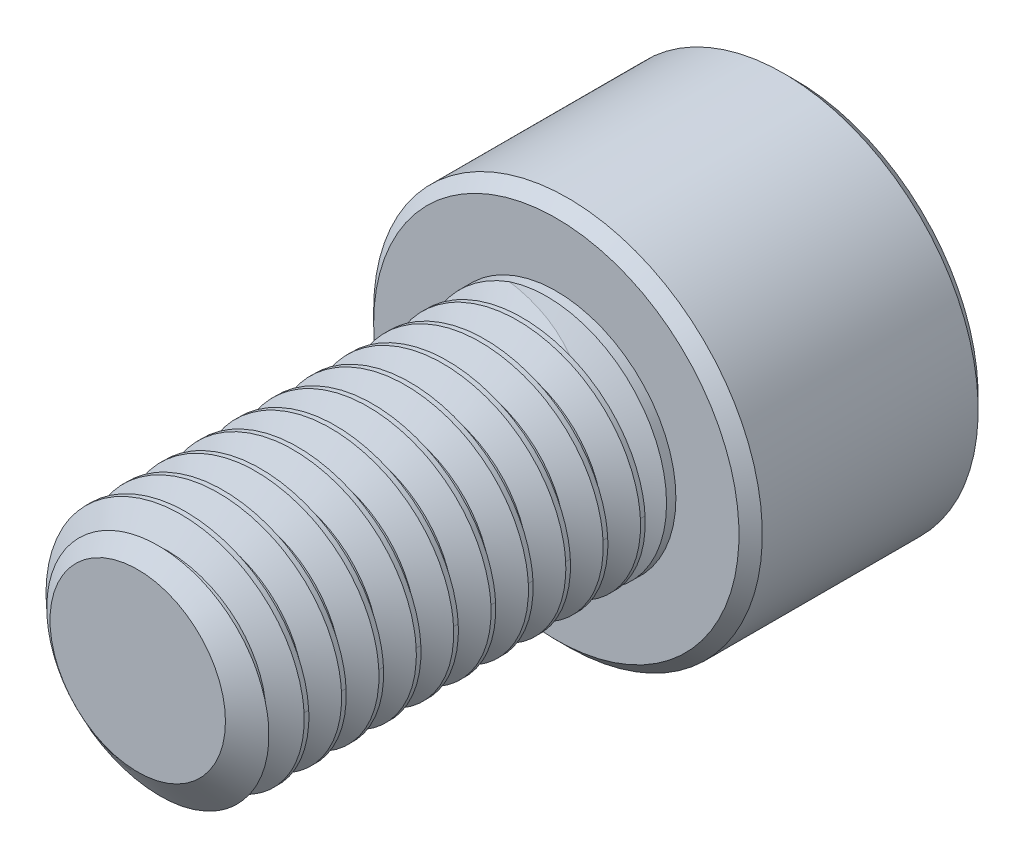
SolidWorks part; units mm, degrees
ref_plane "Front Plane" through (0, 0, 0) normal (0, 0, 1) x (1, 0, 0)
ref_plane "Top Plane" through (0, 0, 0) normal (0, 1, 0) x (1, 0, 0)
ref_plane "Right Plane" through (0, 0, 0) normal (1, 0, 0) x (0, 0, -1)
sketch "Sketch1" plane through (0, 0, 0) normal (0, 0, 1) x (1, 0, 0)
  circle A0 centre (0, 0) radius 4
  dimension "OD" = 8
extrude "Extrude1" add sketch "Sketch1" against normal blind 14
sketch "Sketch2" plane through (0, 0, 0) normal (0, 0, 1) x (1, 0, 0)
  circle A0 centre (0, 0) radius 4 construction
  circle A1 centre (0, 0) radius 4
curve "Helix/Spiral1" pitch 1.25 height 15.25 turns 12.2 parameters "pitch"=1.25
sketch "Sketch3" plane through (0, 0, 0) normal (1, 0, 0) x (0, 0, -1)
  line L0 (-1.0938, 4) -> (-0.625, 3.1881)
  line L1 (-0.625, 3.1881) -> (-0.4688, 3.1881)
  line L2 (-0.4688, 3.1881) -> (0, 4)
  line L3 (-1.0938, 4) -> (0, 4)
  line L4 (-0.5469, 4) -> (-0.5469, 3.1881) construction
  line L5 (-0.8594, 3.5941) -> (-0.2344, 3.5941) construction
  line L6 (0, 4) -> (0, -4) construction
  line L7 (0, -4) -> (14, -4) construction
  point P11 (5.625, -4)
  dimension "D1" = 0.1562
  dimension "D2" = 0.625
  dimension "D3" = 60
  dimension "D4" = 5.625
sweep "Cut-Sweep1" cut profiles "Sketch3" path "Helix/Spiral1"
sketch "Sketch4" plane through (0, 0, 0) normal (1, 0, 0) x (0, 0, -1)
  line L0 (0.7464, 4) -> (0, 2.9341)
  line L1 (0, 2.9341) -> (0, 4)
  line L2 (0.7464, 4) -> (0, 4)
  line L3 (-1.0938, 4) -> (0, 4) construction
  line L4 (0, 0) -> (7.0209, 0) construction
  dimension "D1" = 55
  dimension "D2" = 0.254
revolve "Cut-Revolve1" cut sketch "Sketch4" angle 360 about L4
sketch "Sketch5" plane through (0, 0, 0) normal (1, 0, 0) x (0, 0, -1)
  line L0 (14, -0.9564) -> (14, 3.8508) construction
  line L1 (14, 4) -> (0.1203, 4)
  line L2 (14, 4) -> (14, 0)
  line L3 (14, 0) -> (0.0001, 0)
  line L4 (0.0001, 3.6698) -> (0.0001, 0)
  line L5 (0.1203, 4) -> (0.0001, 3.6698)
  line L6 (0, 0) -> (9.9695, 0) construction
  point P3 (0.0001, 4)
  point P10 (0.0001, 4)
  dimension "D1" = 0.3302
  dimension "Thread min" = 0.0001
  dimension "D3" = 20
revolve "partially thread" [suppressed] add sketch "Sketch5" angle 360 about L6
sketch "Sketch6" plane through (0, 0, -14) normal (0, 0, -1) x (-1, 0, 0)
  circle A0 centre (0, 0) radius 6.5
  dimension "head dia" = 13
extrude "Extrude2" add sketch "Sketch6" along normal blind 8
sketch "Sketch7" plane through (0, 0, -22) normal (0, 0, -1) x (-1, 0, 0)
  line L1 (0, 3.4641) -> (-3, 1.7321)
  line L2 (-3, 1.7321) -> (-3, -1.7321)
  line L3 (-3, -1.7321) -> (0, -3.4641)
  line L4 (0, -3.4641) -> (3, -1.7321)
  line L5 (3, -1.7321) -> (3, 1.7321)
  line L6 (3, 1.7321) -> (0, 3.4641)
  circle A0 centre (0, 0) radius 3 construction
  dimension "hex dia" = 6
extrude "Cut-Extrude1" cut sketch "Sketch7" against normal blind 4.5
sketch "Sketch8" plane through (0, 0, -22) normal (0, 0, -1) x (-1, 0, 0)
  circle A0 centre (0, 0) radius 3.4641
extrude "Cut-Extrude2" cut sketch "Sketch8" against normal through all draft 45
chamfer "Chamfer1" distance 0.39 angle 45 2 edges at (-6.5, 0, -22) (-6.5, 0, -14)
sketch "Sketch9" plane through (0, 0, 0) normal (1, 0, 0) x (0, 0, -1)
  line L0 (0, 4) -> (0, -4) construction
  line L1 (6.875, 4) -> (6.875, -4) construction
  dimension "D1" = 6.875
sketch "Sketch10" plane through (0, 0, 0) normal (1, 0, 0) x (0, 0, -1)
  line L0 (14, 4) -> (14, 0)
  line L1 (14, 4) -> (13.6875, 4)
  line L2 (13.6875, 4) -> (12.0306, 0)
  line L3 (14, 0) -> (12.0306, 0)
  line L4 (14, 6.11) -> (14, -6.11) construction
  dimension "D1" = 22.5
  dimension "D2" = 0.3125
revolve "Revolve1" add sketch "Sketch10" angle 360 about L3
equation "\"D3@Helix/Spiral1\" = \"screw length@Extrude1\"+\"pitch@Helix/Spiral1\""
equation "\"D1@Sketch3\" = \"pitch@Helix/Spiral1\"*.125"
equation "\"D2@Sketch3\" = \"pitch@Helix/Spiral1\"*.5"
equation "\"D1@Cut-Extrude1\" = \"hex dia@Sketch7\"*.75"
equation "\"D1@Chamfer1\" = \"head dia@Sketch6\"*.03"
equation "\"D1@Sketch9\" = \"pitch@Helix/Spiral1\"*5.5"
equation "\"D2@Sketch10\" = \"pitch@Helix/Spiral1\"*.25"
equation "\"D4@Sketch3\" = \"pitch@Helix/Spiral1\"*4.50"
